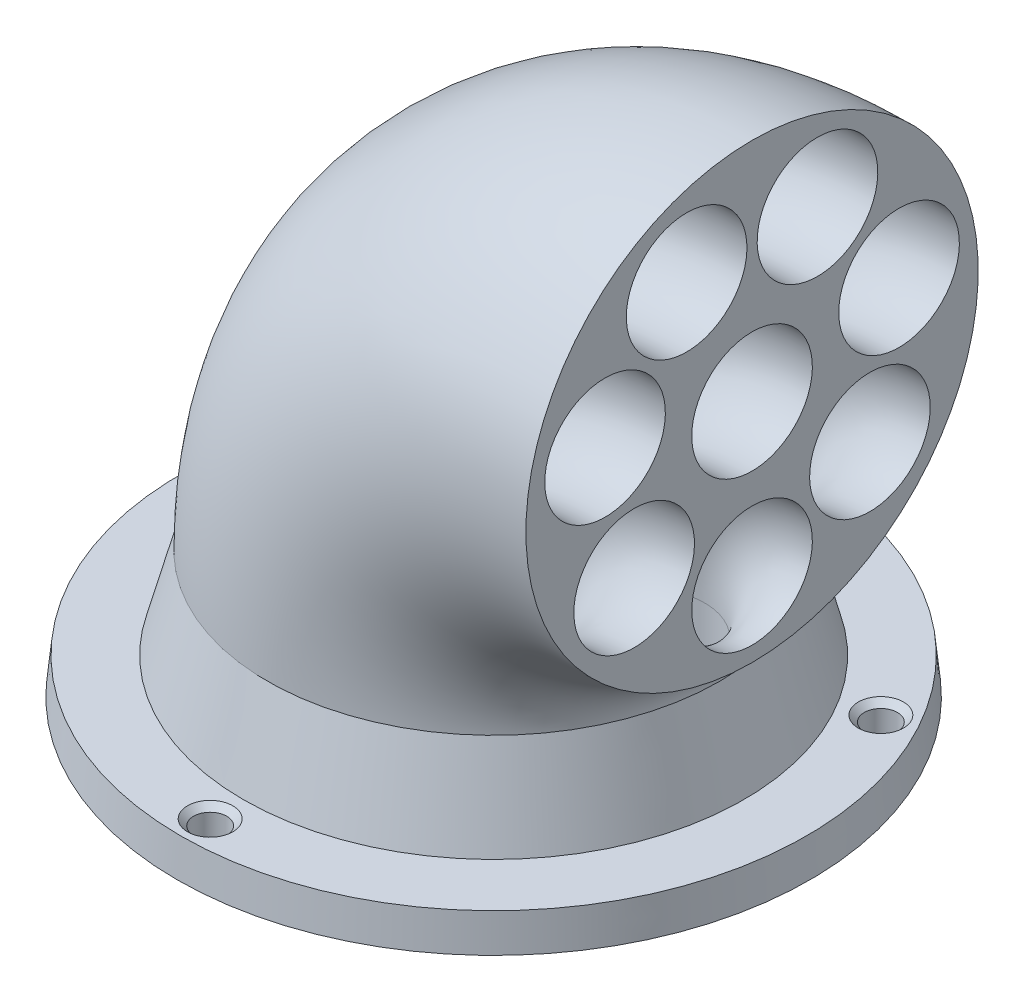
SolidWorks part; units mm, degrees
other "Markup1"
sketch "Sketch2" plane through (25, 12.5, 25) normal (0.1814, 0.4325, 0.8832) x (0.9819, -0.0292, -0.1874)
ref_plane "Front Plane" through (0, 0, 0) normal (0, 0, 1) x (1, 0, 0)
ref_plane "Top Plane" through (0, 0, 0) normal (0, 1, 0) x (1, 0, 0)
ref_plane "Right Plane" through (0, 0, 0) normal (1, 0, 0) x (0, 0, -1)
sketch "Sketch1" plane through (0, 0, 0) normal (0, 1, 0) x (1, 0, 0)
  line L0 (0, 0) -> (12.5, 0)
  line L2 (12.5, 0) -> (7.7936, 9.7729)
  line L3 (7.7936, 9.7729) -> (-2.7815, 12.1866)
  line L4 (-2.7815, 12.1866) -> (-11.2621, 5.4235)
  line L5 (-11.2621, 5.4235) -> (-11.2621, -5.4235)
  line L6 (-11.2621, -5.4235) -> (-2.7815, -12.1866)
  line L7 (-2.7815, -12.1866) -> (7.7936, -9.7729)
  line L8 (7.7936, -9.7729) -> (12.5, 0)
  circle A0 centre (0, 0) radius 26.25
  circle A1 centre (0, 0) radius 5
  circle A2 centre (0, 0) radius 11.2621 construction
  arc A9 (0, -23.5) -> (20.3516, 11.75) centre (0, 0) cw
  circle A13 centre (0, 0) radius 18.75
  circle A17 centre (-2.7815, 12.1866) radius 5
  circle A18 centre (7.7936, 9.7729) radius 5
  circle A19 centre (12.5, 0) radius 5
  circle A20 centre (7.7936, -9.7729) radius 5
  circle A21 centre (-2.7815, -12.1866) radius 5
  circle A22 centre (-11.2621, -5.4235) radius 5
  circle A23 centre (-11.2621, 5.4235) radius 5
  circle A24 centre (0, -23.5) radius 1.375
  circle A25 centre (20.3516, 11.75) radius 1.375
  circle A26 centre (-20.3516, 11.75) radius 1.375
  dimension "D1" = 52.5
  dimension "D2" = 12.5
  dimension "D3" = 37.5
  dimension "D5" = 10
extrude "Boss-Extrude3" add sketch "Sketch1" along normal blind 3 contours A0 A26 A25 A24 A13 | A13 A21 L6 A20 L5 A19 L4 A18 L3 L2 A17 | A21 A17 A1 L2 L3 A18 L4 A19 L5 A20 L6 region at (8.0045, 0, 2.8247) region at (-25.5075, 0, 0) region at (-18.2197, 0, 0)
extrude "Boss-Extrude4" add sketch "Sketch1<6>" along normal blind 7.5 from surface contours A13 A23 L4 A17 L3 A18 L2 A19 L8 A20 L7 A21 L6 A22 L5 | A23 L5 A22 L6 A21 L7 A20 L8 A19 A1 L2 A18 L3 A17 L4 region at (8.0045, 0, 2.8247) region at (-18.2197, 0, 0) starting at face at (-11.2621, 3, -0.4235)
sketch "Sketch1<6>" plane through (0, 0, 0) normal (0, 1, 0) x (1, 0, 0) same geometry as "Sketch1"
fillet "Fillet3" radius 2 1 edges at (0, 3, 18.75) profile chamfer first distance on face at (0, 3, 26.25)
chamfer "Chamfer4" distance 0.5 angle 45 3 edges at (-20.3516, 3, -10.375) (20.3516, 3, -10.375) (0, 3, 24.875)
chamfer "Chamfer5" [suppressed] distance 0.5 angle 45
chamfer "Chamfer6" distance 3 distance2 0.3 1 edges at (0, 3, 26.25) first distance on face at (0, 3, 26.25)
extrude "Boss-Extrude6" add sketch "Sketch1<8>" against normal blind 4 contours L4 A23 L5 | L5 A23 L4 | L6 A22 L5 | L5 A22 L6 | A13 | A19 | A18 | A20 | A1 | A17 | A21 region at (-8.8505, 0, -4.2622) region at (-12.6019, 0, -6.0688) region at (-12.6019, 0, 6.0688) region at (-8.8505, 0, 4.2622)
sketch "Sketch1<8>" plane through (0, 0, 0) normal (0, 1, 0) x (1, 0, 0) same geometry as "Sketch1"
sketch "Sketch3" plane through (0, -4, 0) normal (0, -1, 0) x (1, 0, 0)
  line L0 (0, 0) -> (12.5, 0)
  line L2 (12.5, 0) -> (7.7936, 9.7729)
  line L3 (7.7936, 9.7729) -> (-2.7815, 12.1866)
  line L4 (-2.7815, 12.1866) -> (-11.2621, 5.4235)
  line L5 (-11.2621, 5.4235) -> (-11.2621, -5.4235)
  line L6 (-11.2621, -5.4235) -> (-2.7815, -12.1866)
  line L7 (-2.7815, -12.1866) -> (7.7936, -9.7729)
  line L8 (7.7936, -9.7729) -> (12.5, 0)
  circle A0 centre (0, 0) radius 11.2621 construction
  circle A1 centre (-2.7815, 12.1866) radius 4.75
  circle A2 centre (7.7936, 9.7729) radius 4.75
  circle A3 centre (12.5, 0) radius 4.75
  circle A4 centre (7.7936, -9.7729) radius 4.75
  circle A5 centre (-2.7815, -12.1866) radius 4.75
  circle A6 centre (-11.2621, -5.4235) radius 4.75
  circle A7 centre (-11.2621, 5.4235) radius 4.75
  circle A8 centre (0, 0) radius 4.75
  circle M1 centre (-2.7815, 12.1866) radius 5
  circle M2 centre (-2.7815, -12.1866) radius 5
  circle M3 centre (0, 0) radius 5
  circle M4 centre (7.7936, 9.7729) radius 5
  circle M5 centre (7.7936, -9.7729) radius 5
  circle M6 centre (12.5, 0) radius 5
  circle M7 centre (-11.2621, 5.4235) radius 5
  circle M8 centre (-11.2621, -5.4235) radius 5
extrude "Boss-Extrude7" add sketch "Sketch3" along normal blind 2.5 contours L8 L2 L3 L4 L5 L6 L7 M5 M6 M3 M4 M1 M7 M8 M2 region at (8.0045, -4, -2.8247)
chamfer "Chamfer7" distance 4.75 distance2 2.5 7 edges at (-11.2621, -4, 0) (-7.0218, -4, -8.8051) (2.5061, -4, -10.9797) (10.1468, -4, -4.8864) (10.1468, -4, 4.8864) (2.5061, -4, 10.9797) (-7.0218, -4, 8.8051) first distance on face at (0, -4, 18.75)
chamfer "Chamfer8" distance 4 distance2 2 1 edges at (0, 0, 18.75) first distance on face at (0, -4, 18.75)
sketch "Sketch4" plane through (0, 10.5, 0) normal (0, 1, 0) x (1, 0, 0)
  line L0 (18.75, 0) -> (21.4231, 0)
  line L1 (21.4231, -31.4432) -> (21.4231, 31.4432)
  circle A0 centre (0, 0) radius 18.75
  circle A1 centre (0, 0) radius 5
  circle A2 centre (12.5, 0) radius 5
  circle A3 centre (7.7936, 9.7729) radius 5
  circle A4 centre (-2.7815, 12.1866) radius 5
  circle A5 centre (-11.2621, 5.4235) radius 5
  circle A6 centre (-11.2621, -5.4235) radius 5
  circle A7 centre (-2.7815, -12.1866) radius 5
  circle A8 centre (7.7936, -9.7729) radius 5
  point P28 (18.75, 0)
  point P32 (21.4231, 0)
revolve "Revolve4" add sketch "Sketch4" angle 90 about L1 region at (-18.2197, 10.5, 0)
